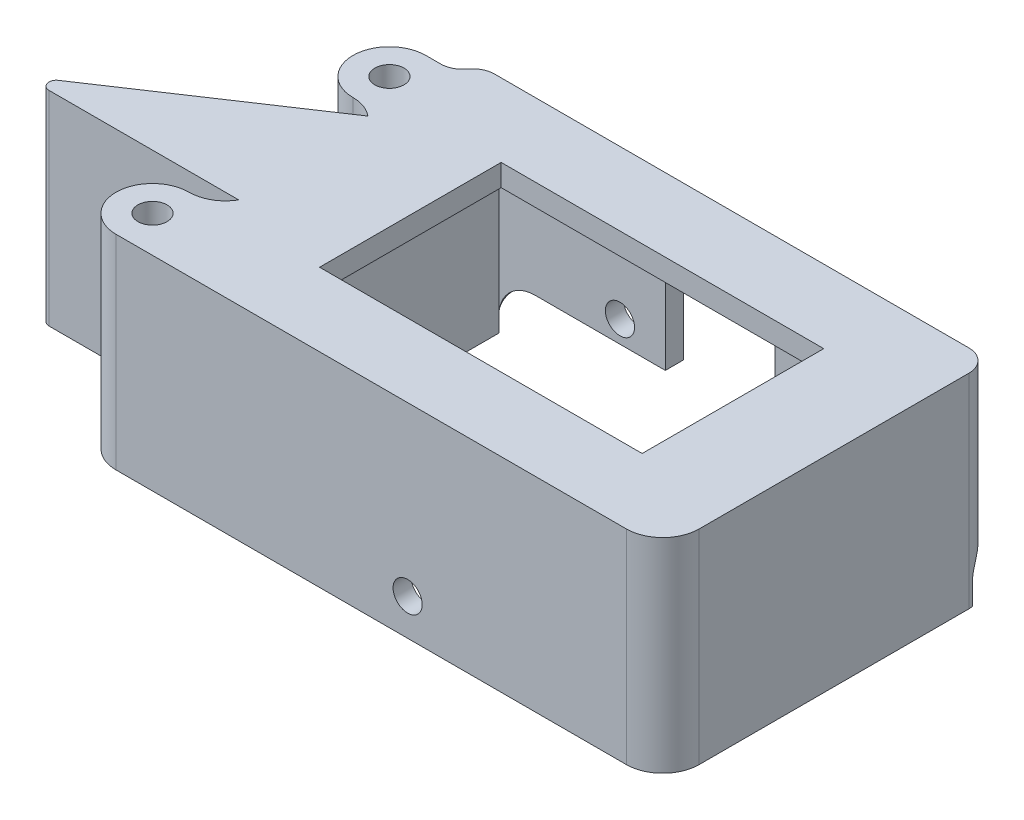
SolidWorks part; units mm, degrees
ref_plane "前视基准面" through (0, 0, 0) normal (0, 0, 1) x (1, 0, 0)
ref_plane "上视基准面" through (0, 0, 0) normal (0, 1, 0) x (1, 0, 0)
ref_plane "右视基准面" through (0, 0, 0) normal (1, 0, 0) x (0, 0, -1)
sketch "草图3" plane through (0, 0, 0) normal (0, 1, 0) x (1, 0, 0)
  line L0 (0, 0) -> (35, 0) construction
  line L1 (35, 0) -> (35, -22.5)
  line L2 (35, -22.5) -> (-35, -22.5)
  line L3 (-35, -22.5) -> (-35, 22.5)
  line L4 (-35, 22.5) -> (35, 22.5)
  line L5 (35, 22.5) -> (35, 0)
extrude "凸台-拉伸1" add sketch "草图3" along normal blind 40
sketch "草图4" plane through (0, 0, 0) normal (0, -1, 0) x (1, 0, 0)
  line L1 (-30, 20) -> (30, 20)
  line L2 (-30, 20) -> (-30, -20)
  line L3 (-30, -20) -> (30, -20)
  line L4 (30, 20) -> (30, -20)
  line L5 (-30, 20) -> (30, -20) construction
  line L6 (-30, -20) -> (30, 20) construction
  point P0 (0, 0)
extrude "切除-拉伸1" cut sketch "草图4" against normal blind 25
sketch "草图5" plane through (-56.5, 0, -20) normal (0, 0, -1) x (-1, 0, 0)
  line L0 (-56.5, 10) -> (-43.125, 10) construction
  line L1 (-26.5, 0) -> (-86.5, 0) construction
  line L2 (-26.5, 0) -> (-26.5, 10) construction
  line L3 (-26.5, 10) -> (-86.5, 10) construction
  line L4 (-86.5, 0) -> (-86.5, 10) construction
  line L5 (-56.5, 10) -> (-56.5, 0) construction
  line L6 (-26.5, 5) -> (-86.5, 5) construction
  line L7 (-86.5, 25) -> (-86.5, 0) construction
  circle A0 centre (-43.125, 10) radius 2
  circle A1 centre (-69.875, 10) radius 2
  point P488 (-56.5, 5)
extrude "切除-拉伸3" cut sketch "草图5" along normal through all
sketch "草图6" plane through (0, 0, 20) normal (0, 0, -1) x (-1, 0, 0)
  line L1 (-30, 0) -> (0, 0) construction
  line L2 (-30, 0) -> (-30, 5) construction
  line L3 (-30, 5) -> (0, 5) construction
  line L4 (0, 0) -> (0, 5) construction
  line L5 (-15, 5) -> (-15, 0) construction
  line L6 (-30, 2.5) -> (0, 2.5) construction
  circle A0 centre (0, 5) radius 2
  point P896 (-15, 2.5)
extrude "切除-拉伸4" cut sketch "草图6" against normal through all
sketch "草图7" plane through (0, 40, 0) normal (0, 1, 0) x (1, 0, 0)
  line L1 (-22.1258, 12.4552) -> (22.1258, 12.4552)
  line L2 (-22.1258, 12.4552) -> (-22.1258, -12.4552)
  line L3 (-22.1258, -12.4552) -> (22.1258, -12.4552)
  line L4 (22.1258, 12.4552) -> (22.1258, -12.4552)
  line L5 (0, -12.4552) -> (0, 12.4552) construction
  line L6 (-22.1258, 0) -> (22.1258, 0) construction
  point P536 (0, 0)
extrude "切除-拉伸5" cut sketch "草图7" against normal through all
sketch "草图8" plane through (0, 0, 0) normal (0, -1, 0) x (1, 0, 0)
  line L0 (-30, -20) -> (30, -20) construction
  line L1 (-35, -20) -> (35.5974, -20)
  line L2 (-35, -20) -> (-35, -22.5)
  line L3 (-35, -22.5) -> (35.5974, -22.5)
  line L4 (35.5974, -20) -> (35.5974, -22.5)
  line L5 (0.2987, -22.5) -> (0.2987, -20) construction
  line L6 (-35, -21.25) -> (35.5974, -21.25) construction
  line L7 (35, -22.5) -> (-35, -22.5) construction
  line L8 (-35, -22.5) -> (-35, 22.5) construction
  point P420 (0.2987, -21.25)
extrude "切除-拉伸6" cut sketch "草图8" against normal blind 7
sketch "草图9" plane through (0, 7, 0) normal (0, -1, 0) x (1, 0, 0)
  line L0 (30, -20) -> (-30, -20) construction
  line L1 (-7.1495, -20) -> (7.9021, -20)
  line L2 (-7.1495, -20) -> (-7.1495, -22.5)
  line L3 (-7.1495, -22.5) -> (7.9021, -22.5)
  line L4 (7.9021, -20) -> (7.9021, -22.5)
  line L5 (0.3763, -22.5) -> (0.3763, -20) construction
  line L6 (-7.1495, -21.25) -> (7.9021, -21.25) construction
  line L7 (-35, -22.5) -> (35, -22.5) construction
  point P248 (0.3763, -21.25)
extrude "切除-拉伸7" cut sketch "草图9" against normal blind 15
sketch "草图10" plane through (0, 40, 0) normal (0, 1, 0) x (1, 0, 0)
  line L1 (35, 22.5) -> (-35, 22.5)
  line L2 (35, 22.5) -> (35, -22.5)
  line L3 (35, -22.5) -> (-35, -22.5)
  line L4 (-35, 22.5) -> (-35, -22.5)
  line L5 (0, -22.5) -> (0, 22.5) construction
  line L6 (35, 0) -> (-35, 0) construction
  point P684 (0, 0)
extrude "切除-拉伸8" cut sketch "草图10" against normal blind 12
sketch "草图11" plane through (0, 0, 0) normal (0, -1, 0) x (1, 0, 0)
  line L5 (-35, 22.5) -> (-45, 22.5) construction
  line L6 (-35, 22.5) -> (-35, -20) construction
  line L11 (-35, -20) -> (-45, -20) construction
  line L12 (-45, 22.5) -> (-45, -20) construction
  line L17 (-40, -20) -> (-40, 22.5) construction
  line L18 (-35, 1.25) -> (-45, 1.25) construction
  line L19 (-45, -20) -> (-35, -20)
  line L20 (-45, -20) -> (-45, -10)
  line L21 (-45, -10) -> (-35, -10)
  line L22 (-35, -20) -> (-35, -10)
  line L23 (-40, -10) -> (-40, -20) construction
  line L24 (-45, -15) -> (-35, -15) construction
  line L25 (-45, 22.5) -> (-35, 22.5)
  line L26 (-45, 22.5) -> (-45, 12.5)
  line L27 (-45, 12.5) -> (-35, 12.5)
  line L28 (-35, 22.5) -> (-35, 12.5)
  line L29 (-40, 12.5) -> (-40, 22.5) construction
  line L30 (-45, 17.5) -> (-35, 17.5) construction
  point P91 (-40, 17.5)
  point P264 (-40, -15)
  point P1490 (-40, 1.25)
  dimension "D1" = 10
  dimension "D2" = 42.5
  dimension "D3" = 10
  dimension "D4" = 10
extrude "凸台-拉伸2" add sketch "草图11" against normal up to surface (28 mm away) up to face at (0, 28, 0)
sketch "草图12" plane through (0, 0, 0) normal (0, -1, 0) x (1, 0, 0)
  line L6 (-45, -20) -> (-35, -20) construction
  line L11 (-45, -20) -> (-45, -10) construction
  line L12 (-45, -10) -> (-35, -10) construction
  line L14 (-35, -20) -> (-35, -10) construction
  line L15 (-40, -10) -> (-40, -20) construction
  line L16 (-45, -15) -> (-35, -15) construction
  line L17 (-45, 22.5) -> (-35, 22.5) construction
  line L18 (-45, 22.5) -> (-45, 12.5) construction
  line L19 (-45, 12.5) -> (-35, 12.5) construction
  line L20 (-35, 22.5) -> (-35, 12.5) construction
  line L21 (-40, 12.5) -> (-40, 22.5) construction
  line L22 (-45, 17.5) -> (-35, 17.5) construction
  circle A2 centre (-40, -15) radius 2
  circle A3 centre (-40, 17.5) radius 2
  point P166 (-40, -15)
  point P169 (-40, 17.5)
extrude "切除-拉伸9" cut sketch "草图12" against normal through all
fillet "圆角1" radius 5 6 edges at (-45, 14, 12.5) (-35, 14, 12.5) (-45, 14, 22.5) (-35, 14, -10) (-45, 14, -10) (-45, 14, -20)
fillet "圆角2" radius 5 1 edges at (35, 14, 22.5)
fillet "圆角4" radius 5 1 edges at (32.5, 7, -20)
fillet "圆角5" radius 5 2 edges at (30, 7, -21.25) (-30, 7, -21.25)
fillet "圆角6" radius 3 4 edges at (0, 25, -20) (30, 25, 0) (0, 25, 20) (-30, 25, 0)
fillet "圆角7" radius 3 3 edges at (-35, 28, -21.25) (-35, 15.3349, -20) (-35, 5.1699, -20.6699)
fillet "圆角8" radius 3 2 edges at (35, 17.5, -22.5) (-35, 17.5, -22.5)
sketch "草图13" plane through (-35, 0, 0) normal (-1, 0, 0) x (0, 0, 1)
  line L0 (22.5, 28) -> (22.5, 0) construction
  line L1 (-5, 28) -> (7.5, 28) construction
  line L2 (-5, 28) -> (-5, 0) construction
  line L3 (-5, 0) -> (7.5, 0) construction
  line L4 (7.5, 28) -> (7.5, 0) construction
  line L5 (1.25, 0) -> (1.25, 28) construction
  line L6 (-5, 14) -> (7.5, 14) construction
  line L7 (-20, 21.5) -> (22.5, 21.5) construction
  line L8 (-20, 21.5) -> (-20, 6.5) construction
  line L9 (-20, 6.5) -> (22.5, 6.5) construction
  line L10 (22.5, 21.5) -> (22.5, 6.5) construction
  line L11 (-20, 21.5) -> (22.5, 6.5) construction
  line L12 (-20, 6.5) -> (22.5, 21.5) construction
  line L13 (-22.5, 7) -> (-22.5, 28) construction
  line L14 (-5, 6.5) -> (-22.5, 6.5)
  line L15 (-5, 6.5) -> (-5, 21.5)
  line L16 (-5, 21.5) -> (-22.5, 21.5)
  line L17 (-22.5, 6.5) -> (-22.5, 21.5)
  line L18 (-13.75, 21.5) -> (-13.75, 6.5) construction
  line L19 (-5, 14) -> (-22.5, 14) construction
  point P4 (1.25, 14)
  point P212 (1.25, 14)
  point P314 (-13.75, 14)
  dimension "D1" = 15
extrude "切除-拉伸10" cut sketch "草图13" along normal through all
sketch "草图14" plane through (0, 0, 0) normal (0, -1, 0) x (1, 0, 0)
  line L0 (-35, -5) -> (-35, 7.5) construction
  line L1 (-47.5, 25) -> (-32.5, 25) construction
  line L2 (-47.5, 25) -> (-47.5, 10) construction
  line L3 (-47.5, 10) -> (-32.5, 10) construction
  line L4 (-32.5, 25) -> (-32.5, 10) construction
  line L5 (-47.5, 25) -> (-32.5, 10) construction
  line L6 (-47.5, 10) -> (-32.5, 25) construction
  line L7 (-47.5, 10) -> (-35, 10) construction
  line L8 (-47.5, 10) -> (-47.5, -10) construction
  line L9 (-47.5, -10) -> (-35, -10) construction
  line L10 (-35, 10) -> (-35, -10) construction
  line L11 (-41.25, -10) -> (-41.25, 10) construction
  line L12 (-47.5, 0) -> (-35, 0) construction
  line L13 (-65, 10) -> (-35, 10)
  line L14 (-35, -10) -> (-65, -10) construction
  line L15 (-35, -10) -> (-35, 10) construction
  line L16 (-35, 10) -> (-65, 10) construction
  line L17 (-65, -10) -> (-65, 10) construction
  line L18 (-50, 10) -> (-50, -10) construction
  line L19 (-35, 0) -> (-65, 0) construction
  line L20 (-35, 10) -> (-35, -10)
  line L21 (-35, -10) -> (-65, 10)
  point P0 (-40, 17.5)
  point P285 (-41.25, 0)
  point P346 (-50, 0)
  dimension "D1" = 15
  dimension "D2" = 15
  dimension "D3" = 20
  dimension "D4" = 30
extrude "凸台-拉伸3" add sketch "草图14" against normal up to surface (28 mm away) up to face at (-40, 28, -17)
fillet "圆角11" radius 1 1 edges at (-65, 14, 10)
